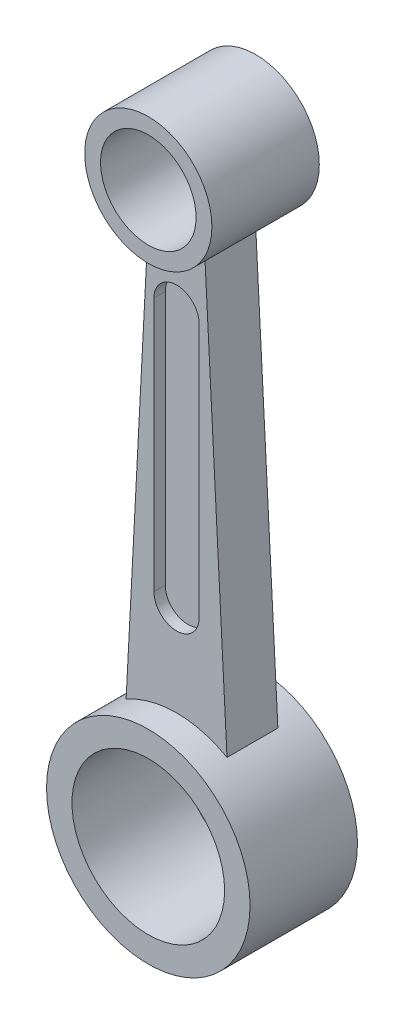
SolidWorks part; units mm, degrees
ref_plane "Front Plane" through (0, 0, 0) normal (0, 0, 1) x (1, 0, 0)
ref_plane "Top Plane" through (0, 0, 0) normal (0, 1, 0) x (1, 0, 0)
ref_plane "Right Plane" through (0, 0, 0) normal (1, 0, 0) x (0, 0, -1)
sketch "Sketch1" plane through (0, 0, 0) normal (0, 0, 1) x (1, 0, 0)
  line L0 (0, 0) -> (0, -201.2) construction
  line L1 (-10, -20.1556) -> (-17.8497, -169.9368)
  line L2 (10, -20.1556) -> (17.8497, -169.9368)
  circle A0 centre (0, 0) radius 16.9
  circle A1 centre (0, 0) radius 22.5
  circle A2 centre (0, -201.2) radius 36
  circle A3 centre (0, -201.2) radius 27
  dimension "D1" = 72
  dimension "D2" = 54
  dimension "D4" = 45
  dimension "D5" = 33.8
  dimension "D3" = 201.2
  dimension "D6" = 20
  dimension "D7" = 6
extrude "Boss-Extrude1" add sketch "Sketch1" along normal mid plane 38 contours A0 A1 | A2 A3 region at (-11.5231, 18.5805, 0) region at (0, -166.2182, 0)
extrude "Boss-Extrude2" add sketch "Sketch1<3>" along normal mid plane 18 contours L0 A1 L1 A2 | A1 L0 A2 L2 region at (7.1843, -100.8455, 0) region at (-7.1843, -100.8455, 0)
sketch "Sketch1<3>" plane through (0, 0, 0) normal (0, 0, 1) x (1, 0, 0) same geometry as "Sketch1"
sketch "Sketch2" plane through (0, 0, 9) normal (0, 0, 1) x (1, 0, 0)
  line L0 (0, 0) -> (0, -174.2) construction
  line L1 (0, -132.1) -> (0, -42.1) construction
  line L2 (-8, -132.1) -> (-8, -42.1)
  line L3 (8, -132.1) -> (8, -42.1)
  circle A0 centre (0, -201.2) radius 27 construction
  arc A1 (-8, -132.1) -> (8, -132.1) centre (0, -132.1) ccw
  arc A2 (8, -42.1) -> (-8, -42.1) centre (0, -42.1) ccw
  point P8 (0, -87.1)
  dimension "D2" = 8
  dimension "D1" = 90
extrude "Cut-Extrude1" cut sketch "Sketch2" against normal blind 4
mirror "Mirror1" about plane through (0, 0, 0) normal (0, 0, 1) of "Cut-Extrude1"
